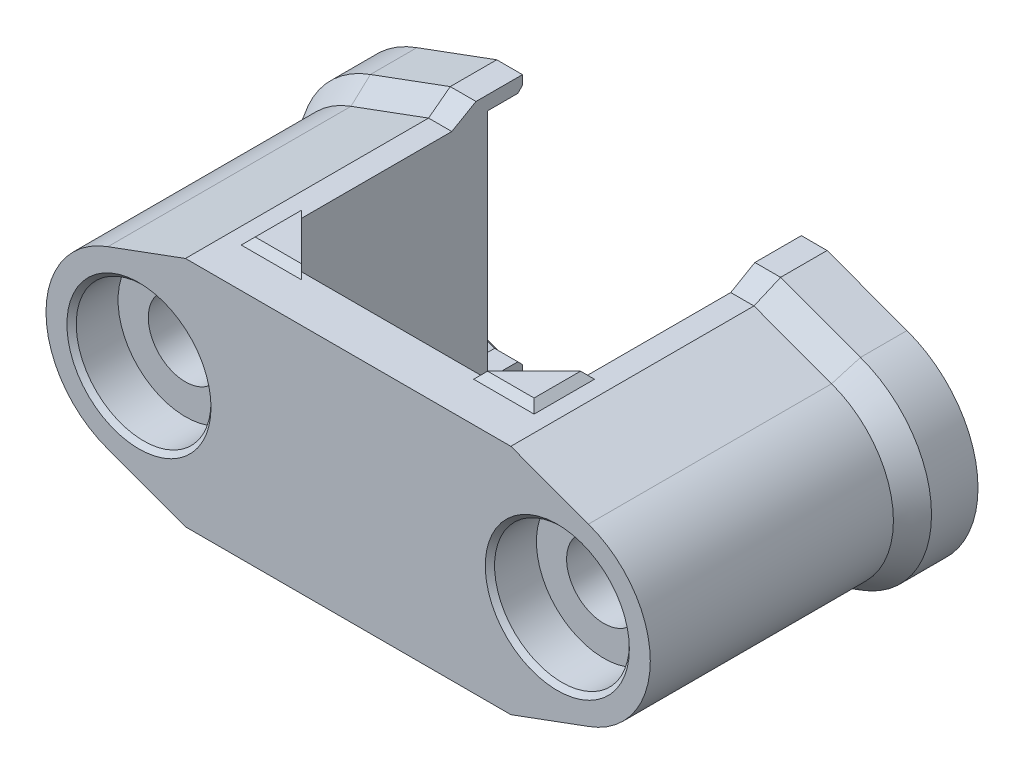
SolidWorks part; units mm, degrees
material "PVC hart"
ref_plane "Ebene vorne" through (0, 0, 0) normal (0, 0, 1) x (1, 0, 0)
ref_plane "Ebene oben" through (0, 0, 0) normal (0, 1, 0) x (1, 0, 0)
ref_plane "Ebene rechts" through (0, 0, 0) normal (1, 0, 0) x (0, 0, -1)
sketch "Skizze2" plane through (0, 0, 0) normal (0, 0, 1) x (1, 0, 0)
  line L0 (0, 0) -> (0, 4.16) construction
  line L1 (9, 0) -> (-9, 0) construction
  line L2 (-6, -2.6458) -> (-6, -5)
  line L7 (6, 5) -> (-6, 5)
  line L8 (6, 5) -> (6, 2.6458)
  line L9 (6, -5) -> (-6, -5)
  line L10 (-6, 5) -> (-6, 2.6458)
  line L11 (6, 5) -> (-6, -5) construction
  line L12 (6, -5) -> (-6, 5) construction
  line L13 (6, -2.6458) -> (6, -5)
  circle A0 centre (-9, 0) radius 1.6
  arc A1 (-6, 2.6458) -> (-6, -2.6458) centre (-9, 0) ccw
  circle A2 centre (9, 0) radius 1.6
  arc A3 (6, 2.6458) -> (6, -2.6458) centre (9, 0) cw
  dimension "D1" = 3.2
  dimension "D2" = 8
  dimension "D3" = 18
  dimension "D4" = 10
  dimension "D5" = 12
extrude "Aufsatz-Linear austragen1" add sketch "Skizze2" along normal blind 12
ref_plane "Ebene1" through (0, 0, 0) normal (0, -1, 0) x (-1, 0, 0)
sketch "Skizze3" plane through (0, 0, 0) normal (0, -1, 0) x (-1, 0, 0)
  line L0 (6, 0) -> (-6, 0) construction
  line L1 (-6, 0) -> (6, 0)
  line L2 (-6, 0) -> (-6, -10)
  line L3 (-6, -10) -> (6, -10)
  line L4 (6, 0) -> (6, -10)
  line L5 (0, -10) -> (0, 0) construction
  dimension "D1" = 10
  dimension "D2" = 12
extrude "Schnitt-Linear austragen1" cut sketch "Skizze3" against normal through all and the other way through all
sketch "Skizze4" plane through (0, 0, 12) normal (0, 0, 1) x (1, 0, 0)
  line L0 (0, 5) -> (0, 0) construction
  line L1 (6, 5) -> (-6, 5) construction
  line L2 (-6, 5) -> (-7, 5)
  line L3 (-7, 5) -> (-10.3385, 3.7694)
  line L4 (-6, 5) -> (-6, 2.6458) construction
  line L5 (-6, 5) -> (-6, 2.6458)
  line L6 (-1.1, 0) -> (1.1, 0) construction
  line L7 (-6, -5) -> (-6, -2.6458)
  line L8 (-7, -5) -> (-10.3385, -3.7694)
  line L9 (-6, -5) -> (-7, -5)
  line L10 (6, -5) -> (7, -5)
  line L11 (7, -5) -> (10.3385, -3.7694)
  line L12 (6, -5) -> (6, -2.6458)
  line L13 (6, 5) -> (6, 2.6458)
  line L14 (7, 5) -> (10.3385, 3.7694)
  line L15 (6, 5) -> (7, 5)
  arc A0 (-6, 2.6458) -> (-6, -2.6458) centre (-9, 0) ccw construction
  arc A1 (-6, 2.6458) -> (-10.3385, 3.7694) centre (-9, 0) ccw
  arc A2 (-6, -2.6458) -> (-10.3385, -3.7694) centre (-9, 0) cw
  arc A3 (6, -2.6458) -> (10.3385, -3.7694) centre (9, 0) ccw
  arc A4 (6, 2.6458) -> (10.3385, 3.7694) centre (9, 0) cw
  arc M5 (-6, 2.6458) -> (-6, -2.6458) centre (-9, 0) ccw
  line M6 (-6, -2.6458) -> (-6, -5)
  line M8 (6, -5) -> (6, -2.6458)
  arc M9 (6, -2.6458) -> (6, 2.6458) centre (9, 0) ccw
  line M10 (6, 2.6458) -> (6, 5)
  line M12 (-6, 5) -> (-6, 2.6458)
  dimension "D1" = 1
extrude "Aufsatz-Linear austragen2" add sketch "Skizze4" against normal through all contours L2 L3 M5 M12 | L9 L8 M6 M5 | L15 L14 M10 M9 | L10 L11 M9 M8 region at (-7.1267, 4.1275, 12) region at (-7.1267, -4.1275, 12) region at (7.1267, -4.1275, 12) region at (7.1267, 4.1275, 12)
sketch "Skizze5" plane through (0, -5, 0) normal (0, -1, 0) x (1, 0, 0)
  line L0 (-6, 10) -> (-4, 10)
  line L1 (6, 10) -> (-6, 10) construction
  line L2 (-4, 10) -> (-6, 8)
  line L3 (-6, 0) -> (-6, 10) construction
  line L4 (-6, 8) -> (-6, 10)
  line L5 (0, 12) -> (0, 10) construction
  line L6 (-7, 12) -> (7, 12) construction
  line L7 (6, 8) -> (6, 10)
  line L8 (4, 10) -> (6, 8)
  line L9 (6, 10) -> (4, 10)
  dimension "D1" = 2
extrude "Aufsatz-Linear austragen3" add sketch "Skizze5" against normal blind 0.4 and the other way blind 0.3
mirror "Spiegeln1" about plane through (0, 0, 0) normal (0, -1, 0) of "Aufsatz-Linear austragen3"
chamfer "Fase3" distance 0.3 angle 45 8 edges at (6, -5, 9) (5, -5, 10) (-6, -5, 9) (-5, -5, 10) (6, 5, 9) (5, 5, 10) (-5, 5, 10) (-6, 5, 9)
ref_plane "Ebene2" through (0, 0, -1.5) normal (0, 0, -1) x (-1, 0, 0)
sketch "Skizze6" plane through (0, 0, -1.5) normal (0, 0, -1) x (-1, 0, 0)
  line L0 (6, -5) -> (7, -5) construction
  line L1 (7, -5) -> (10.3385, -3.7694) construction
  line L2 (7, 5) -> (10.3385, 3.7694) construction
  line L3 (6, 5) -> (7, 5) construction
  line L4 (6, -5) -> (7, -5)
  line L5 (7, -5) -> (10.3385, -3.7694)
  line L6 (7, 5) -> (10.3385, 3.7694)
  line L7 (6, 5) -> (7, 5)
  line L8 (6, 5.6) -> (7.1071, 5.6)
  line L9 (7.1071, 5.6) -> (10.5428, 4.3336)
  line L10 (7.1071, -5.6) -> (10.5428, -4.3336)
  line L11 (6, -5.6) -> (7.1071, -5.6)
  line L12 (6, 5.6) -> (6, 5)
  line L13 (6, -5) -> (6, -5.6)
  line L14 (0, 5) -> (0, -5) construction
  line L15 (-4, 5) -> (4, 5) construction
  line L16 (-4, -5) -> (4, -5) construction
  line L17 (-6, -5) -> (-6, -5.6)
  line L18 (-6, 5.6) -> (-6, 5)
  line L19 (-6, -5.6) -> (-7.1071, -5.6)
  line L20 (-7.1071, -5.6) -> (-10.5428, -4.3336)
  line L21 (-7.1071, 5.6) -> (-10.5428, 4.3336)
  line L22 (-6, 5.6) -> (-7.1071, 5.6)
  line L23 (-6, 5) -> (-7, 5)
  line L24 (-7, 5) -> (-10.3385, 3.7694)
  line L25 (-7, -5) -> (-10.3385, -3.7694)
  line L26 (-6, -5) -> (-7, -5)
  arc A0 (10.3385, -3.7694) -> (10.3385, 3.7694) centre (9, 0) ccw construction
  arc A1 (10.3385, -3.7694) -> (10.3385, 3.7694) centre (9, 0) ccw
  arc A2 (10.5428, -4.3336) -> (10.5428, 4.3336) centre (9, 0) ccw
  arc A3 (-10.5428, -4.3336) -> (-10.5428, 4.3336) centre (-9, 0) cw
  arc A4 (-10.3385, -3.7694) -> (-10.3385, 3.7694) centre (-9, 0) cw
  dimension "D1" = 0.6
extrude "Aufsatz-Linear austragen4" add sketch "Skizze6" against normal blind 2
chamfer "Fase1" distance 0.6 angle 60 9 edges at (-6.5, 5, 0.5) (-8.6692, 4.3847, 0.5) (-13, 0, 0.5) (-6.5, -5, 0.5) (-8.6692, -4.3847, 0.5) (6.5, -5, 0.5) (8.6692, -4.3847, 0.5) (8.6692, 4.3847, 0.5) (6.5, 5, 0.5) first distance on face at (-8.3079, 0, 0.5) first distance on face at (8.3079, 0, 0.5)
sketch "Skizze7" plane through (0, 0, 12) normal (0, 0, 1) x (1, 0, 0)
  circle A0 centre (-9, 0) radius 2.9
  circle A1 centre (9, 0) radius 2.9
  dimension "D1" = 5.8
extrude "Schnitt-Linear austragen2" cut sketch "Skizze7" against normal blind 2
chamfer "Fase2" distance 0.2 angle 45 13 edges at (-6.5, -5, -1.5) (-8.6692, -4.3847, -1.5) (-8.6692, 4.3847, -1.5) (-6.5, 5, -1.5) (6.5, -5, -1.5) (8.6692, -4.3847, -1.5) (13, 0, -1.5) (8.6692, 4.3847, -1.5) (6.5, 5, -1.5) (7.4, 0, 0) (-7.4, 0, 0) (-6.1, 0, 12) (11.9, 0, 12)
